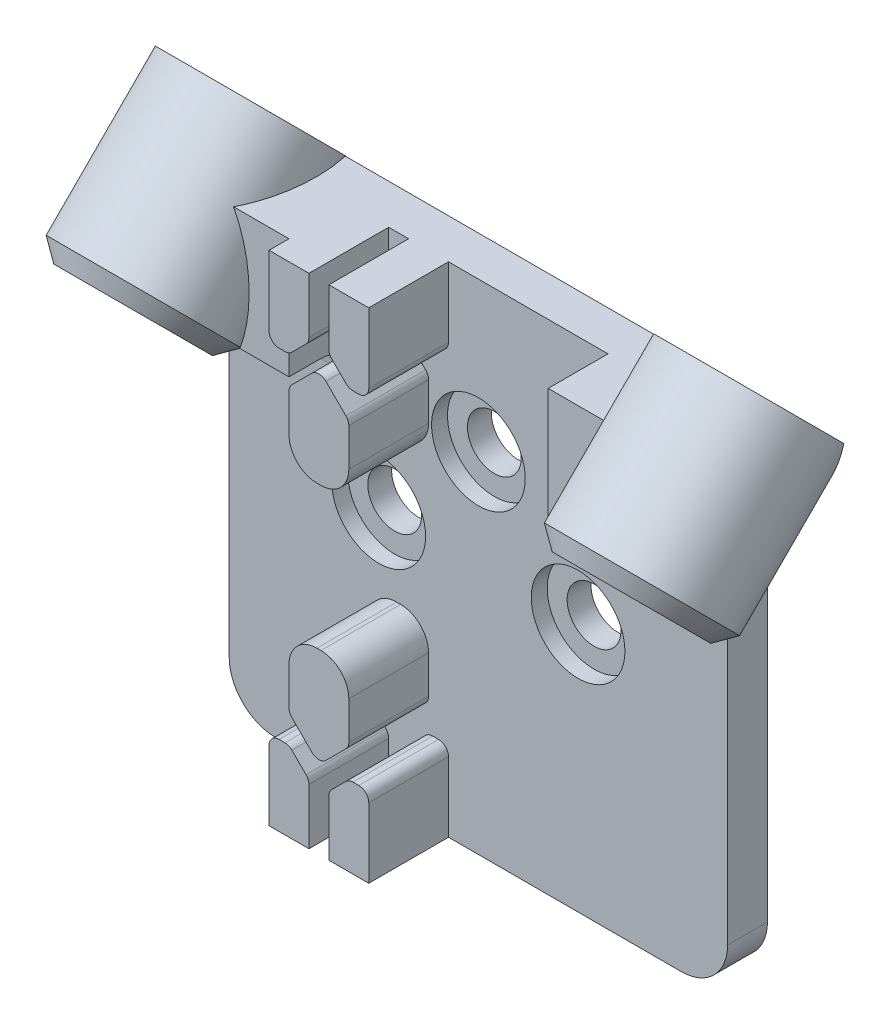
SolidWorks part; units mm, degrees
ref_plane "Piano frontale" through (0, 0, 0) normal (0, 0, 1) x (1, 0, 0)
ref_plane "Piano superiore" through (0, 0, 0) normal (0, 1, 0) x (1, 0, 0)
ref_plane "Piano destro" through (0, 0, 0) normal (1, 0, 0) x (0, 0, -1)
sketch "Schizzo1" plane through (0, 0, 0) normal (0, 0, 1) x (1, 0, 0)
  line L0 (25, 3.35) -> (19.75, 3.35) construction
  line L1 (25, 3.35) -> (25, 20.365)
  line L2 (20.365, 25) -> (-20.365, 25)
  line L3 (-25, 20.365) -> (-25, 3.35)
  line L4 (-19.75, 3.35) -> (-25, 3.35) construction
  line L5 (-19.75, -3.35) -> (-19.75, 3.35) construction
  line L6 (-25, -3.35) -> (-19.75, -3.35) construction
  line L7 (-25, -3.35) -> (-25, -20.365)
  line L8 (-20.365, -25) -> (20.365, -25)
  line L9 (25, -20.365) -> (25, -3.35)
  line L10 (19.75, -3.35) -> (25, -3.35) construction
  line L11 (19.75, 3.35) -> (19.75, -3.35) construction
  line L12 (0, 25) -> (0, -25) construction
  line L13 (25, 3.35) -> (25, -3.35)
  line L14 (-25, 3.35) -> (-25, -3.35)
  arc A0 (25, 20.365) -> (20.365, 25) centre (20.365, 20.365) ccw
  arc A1 (-20.365, 25) -> (-25, 20.365) centre (-20.365, 20.365) ccw
  arc A2 (-25, -20.365) -> (-20.365, -25) centre (-20.365, -20.365) ccw
  arc A3 (20.365, -25) -> (25, -20.365) centre (20.365, -20.365) ccw
  circle A4 centre (-15, -15.95) radius 5.05 construction
  circle A5 centre (15, -15.95) radius 5.05 construction
  circle A6 centre (15, 15.95) radius 6 construction
  circle A7 centre (-15, 15.95) radius 6 construction
  circle A8 centre (0, 10) radius 2.7
  circle A9 centre (-10, 0) radius 2.7
  circle A10 centre (0, 0) radius 2.7 construction
  circle A11 centre (0, -10) radius 2.7 construction
  circle A12 centre (10, 0) radius 2.7
  point P0 (25, 11.8575)
  dimension "D2" = 5.4
  dimension "D7" = 12
  dimension "D12" = 4.635
  dimension "D14" = 10.1
  dimension "D15" = 19.75
  dimension "D16" = 3.35
  dimension "D1" = 50
  dimension "D3" = 10
  dimension "D4" = 10
  dimension "D5" = 10
  dimension "D6" = 10
  dimension "D8" = 30
  dimension "D9" = 31.9
  dimension "D10" = 9.05
  dimension "D11" = 10
  dimension "D13" = 50
extrude "Estrusione-Estrusione1" add sketch "Schizzo1" along normal blind 4
sketch "Schizzo4" plane through (0, 0, 4) normal (0, 0, 1) x (1, 0, 0)
  line L0 (0, 25) -> (0, -25) construction
  line L1 (20.365, 25) -> (-20.365, 25) construction
  line L2 (-20.365, -25) -> (20.365, -25) construction
  line L3 (-8, 25) -> (-8, -25) construction
  line L4 (-7, -25) -> (-7, -19)
  line L5 (-13, -25) -> (-9, -25)
  line L6 (-13, -25) -> (-13, -17)
  line L7 (-13, -17) -> (-11, -17)
  line L8 (-9, -25) -> (-9, -19)
  line L9 (-3, -17) -> (-5, -17)
  line L10 (-3, -25) -> (-3, -17)
  line L11 (-3, -25) -> (-7, -25)
  line L12 (-11, -17) -> (-9, -19)
  line L13 (-5, -17) -> (-7, -19)
  line L14 (-8, -17.1716) -> (-11, -14.1716)
  line L15 (-11, -14.1716) -> (-11, -7.1716)
  line L16 (-11, -7.1716) -> (-5, -7.1716)
  line L17 (-5, -7.1716) -> (-5, -14.1716)
  line L18 (-5, -14.1716) -> (-8, -17.1716)
  dimension "D1" = 8
  dimension "D2" = 8
  dimension "D3" = 4
  dimension "D4" = 1
  dimension "D5" = 2
  dimension "D6" = 135
  dimension "D7" = 2
  dimension "D8" = 3
  dimension "D9" = 7
extrude "Estrusione-Estrusione4" add sketch "Schizzo4" along normal blind 8
fillet "Raccordo1" radius 1 9 edges at (-3, -17, 8) (-5, -17, 8) (-13, -17, 8) (-11, -17, 8) (-5, -14.1716, 8) (-11, -14.1716, 8) (-8, -17.1716, 8) (-7, -19, 8) (-9, -19, 8)
fillet "Raccordo2" radius 2.8 2 edges at (-5, -7.1716, 8) (-11, -7.1716, 8)
ref_axis "Assi1" through (0, 0, 0) along (0, 0, 1)
mirror "Specchia1" about plane through (0, 0, 0) normal (0, 1, 0) of "Raccordo2", "Raccordo1", "Estrusione-Estrusione4"
sketch "Schizzo5" plane through (0, 0, 4) normal (0, 0, 1) x (1, 0, 0)
  circle A0 centre (-10, 0) radius 4.7
  circle A1 centre (10, 0) radius 4.7
  circle A2 centre (10, 0) radius 2.7 construction
  circle A3 centre (0, 10) radius 4.7
  dimension "D1" = 9.4
extrude "Taglio-Estrusione1" cut sketch "Schizzo5" against normal blind 1.6
sketch "Schizzo6" plane through (0, 0, 4) normal (0, 0, 1) x (1, 0, 0)
  line L0 (-25, 5) -> (25, 5) construction
  line L1 (-25, 20.365) -> (-25, -20.365) construction
  line L2 (25, -20.365) -> (25, 20.365) construction
  line L3 (-13, 25) -> (-20.365, 25) construction
  dimension "D1" = 20
ref_plane "Piano2" through (0, 0.5, -0.5) normal (0, -0.7071, 0.7071) x (1, 0, 0)
sketch "Schizzo9" plane through (0, 0, 4) normal (0, 0, 1) x (1, 0, 0)
  line L0 (13, 25) -> (20.365, 25)
  line L1 (20.365, 25) -> (-3, 25) construction
  line L2 (25, 20.365) -> (25, 13)
  line L3 (25, -20.365) -> (25, 20.365) construction
  line L4 (25, 13) -> (13, 13)
  line L5 (13, 13) -> (13, 25)
  line L6 (0, 0) -> (0, 25) construction
  line L7 (-13, 13) -> (-13, 25)
  line L8 (-25, 13) -> (-13, 13)
  line L9 (-25, 20.365) -> (-25, 13)
  line L10 (-13, 25) -> (-20.365, 25)
  arc A0 (25, 20.365) -> (20.365, 25) centre (20.365, 20.365) ccw construction
  arc A1 (25, 20.365) -> (20.365, 25) centre (20.365, 20.365) ccw
  arc A2 (-25, 20.365) -> (-20.365, 25) centre (-20.365, 20.365) cw
  dimension "D1" = 12
extrude "Estrusione-Estrusione6" add sketch "Schizzo9" along normal blind 6
sketch "Schizzo8" plane through (0, 0.5, -0.5) normal (0, -0.7071, 0.7071) x (1, 0, 0)
  line L0 (0, 0) -> (0, 50.8367) construction
  line L1 (0, 0) -> (0, 16.5) construction
  circle A0 centre (-25, 20) radius 8
  circle A1 centre (25, 20) radius 8
  dimension "D1" = 16
  dimension "D2" = 25
  dimension "D3" = 20
extrude "Estrusione-Estrusione5" add sketch "Schizzo8" against normal blind 17
sketch "Schizzo11" plane through (0, -25, 0) normal (0, -1, 0) x (1, 0, 0)
  line L1 (-51.4628, 0) -> (53.963, 0)
  line L2 (-51.4628, 0) -> (-51.4628, -17.7396)
  line L3 (-51.4628, -17.7396) -> (53.963, -17.7396)
  line L4 (53.963, 0) -> (53.963, -17.7396)
extrude "Taglio-Estrusione3" cut sketch "Schizzo11" against normal blind 65
fillet "Raccordo3" radius 2.8 2 edges at (18.7116, 13, 4) (-18.7116, 13, 4)
chamfer "Smusso3" distance 1.5 angle 45 2 edges at (25, 20.299, 19.299) (-25, 8.9853, 7.9853)
sketch "Schizzo13" plane through (0, 0.5, -0.5) normal (0, -0.7071, 0.7071) x (1, 0, 0)
  line L0 (-25, 13.5) -> (-25, 26.5) construction
  circle A0 centre (-25, 20) radius 6.5 construction
ref_plane "Piano3" through (-25, 0, 0) normal (1, 0, 0) x (0, 0.7071, 0.7071)
sketch "Schizzo14" plane through (-25, 0, 0) normal (1, 0, 0) x (0, 0.7071, 0.7071)
  line L0 (13.5, -0.7071) -> (26.5, -0.7071) construction
  line L1 (20, -0.7071) -> (20, 11.6414) construction
  line L2 (20, -3.2071) -> (20, 7.7929) construction
  line L3 (20, -3.2071) -> (20, 7.7929)
  arc A0 (20, 7.7929) -> (20, -3.2071) centre (20, 2.2929) ccw
  dimension "D1" = 11
  dimension "D2" = 3
revolve "Taglia-Rivoluzione1" cut sketch "Schizzo14" angle 360 about L3
mirror "Specchia2" about plane through (0, 0, 0) normal (1, 0, 0) of "Taglia-Rivoluzione1"
sketch "Schizzo15" plane through (0, 0.5, -0.5) normal (0, -0.7071, 0.7071) x (1, 0, 0)
  line L0 (-25, 13.5) -> (-25, 26.5) construction
  circle A0 centre (-25, 20) radius 1.7
  circle A1 centre (25, 20) radius 1.7
  dimension "D1" = 3.4
extrude "Taglio-Estrusione4" cut sketch "Schizzo15" against normal blind 65
sketch "Schizzo16" plane through (0, 12.5208, -12.5208) normal (0, 0.7071, -0.7071) x (1, 0, 0)
  line L0 (-25, -13.5) -> (-25, -26.5) construction
  circle A0 centre (-25, -20) radius 3.7
  circle A1 centre (25, -20) radius 3.7
  dimension "D1" = 7.4
extrude "Taglio-Estrusione5" cut sketch "Schizzo16" against normal blind 5
